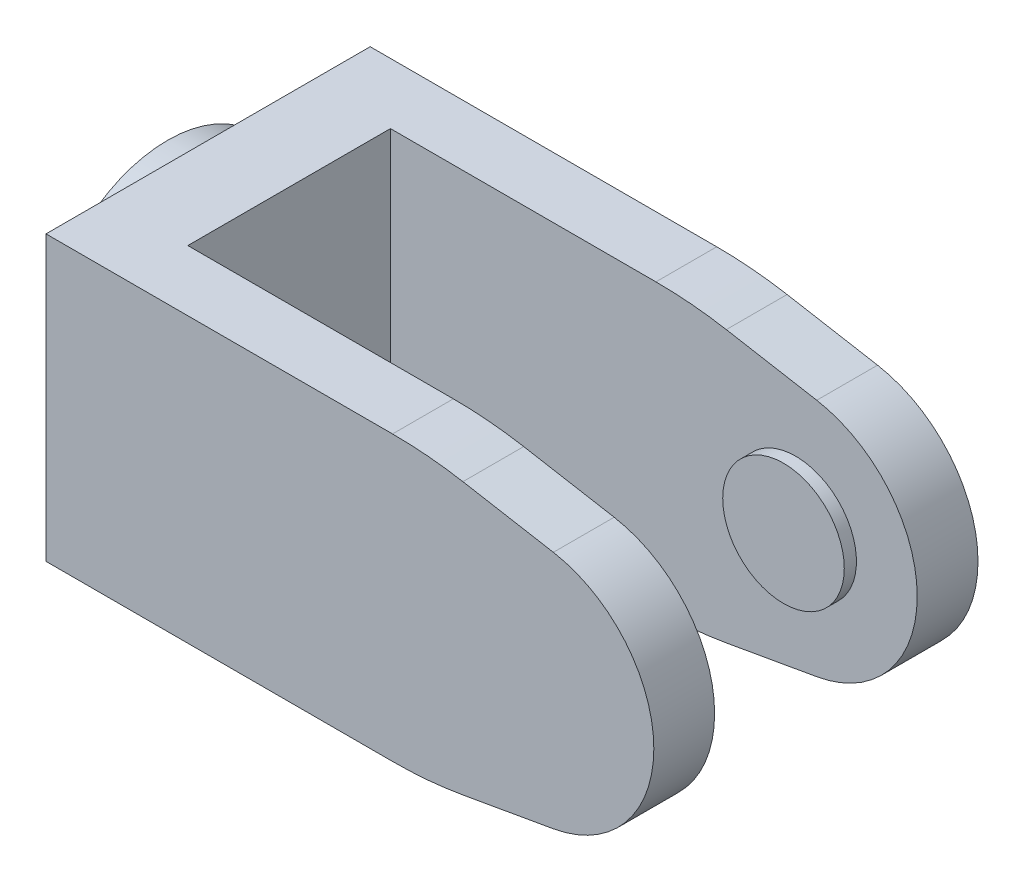
SolidWorks part; units mm, degrees
ref_plane "Front Plane" through (0, 0, 0) normal (0, 0, 1) x (1, 0, 0)
ref_plane "Top Plane" through (0, 0, 0) normal (0, 1, 0) x (1, 0, 0)
ref_plane "Right Plane" through (0, 0, 0) normal (1, 0, 0) x (0, 0, -1)
sketch "Sketch1" plane through (0, 0, 0) normal (0, 0, 1) x (1, 0, 0)
  line L0 (-54.1597, -43.8848) -> (40.1086, -43.8848)
  line L1 (40.1086, -43.8848) -> (71.0498, -38.4291)
  line L2 (71.0498, 20.6594) -> (40.1086, 26.1152)
  line L3 (40.1086, 26.1152) -> (-54.1597, 26.1152)
  line L4 (-54.1597, 26.1152) -> (-54.1597, -43.8848)
  arc A0 (71.0498, -38.4291) -> (71.0498, 20.6594) centre (65.8403, -8.8848) ccw
  dimension "D1" = 170
  dimension "D2" = 170
  dimension "D3" = 70
  dimension "D4" = 120
extrude "Boss-Extrude1" add sketch "Sketch1" along normal mid plane 80
sketch "Sketch2" plane through (0, 0, 0) normal (0, 1, 0) x (1, 0, 0)
  line L0 (40.1086, 40) -> (-54.1597, 40) construction
  line L1 (-34.1597, 25) -> (120.6231, 25)
  line L2 (-34.1597, 25) -> (-34.1597, -25)
  line L3 (-34.1597, -25) -> (120.6231, -25)
  line L4 (120.6231, 25) -> (120.6231, -25)
  line L5 (40.1086, -40) -> (-54.1597, -40) construction
  line L6 (-54.1597, -40) -> (-54.1597, 40) construction
  point P6 (0, 0)
  dimension "D1" = 154.7827
  dimension "D2" = 15
  dimension "D3" = 15
  dimension "D4" = 20
extrude "Cut-Extrude1" cut sketch "Sketch2" against normal through all
extrude "Cut-Extrude2" cut sketch "Sketch2<2>" along normal through all
sketch "Sketch2<2>" plane through (0, 0, 0) normal (0, 1, 0) x (1, 0, 0) same geometry as "Sketch2"
sketch "Sketch3" plane through (0, 0, -25) normal (0, 0, 1) x (1, 0, 0)
  circle A0 centre (65.8403, -8.8848) radius 15
  dimension "D1" = 30
extrude "Boss-Extrude2" add sketch "Sketch3" along normal blind 3
mirror "Mirror1" about plane through (0, 0, 0) normal (0, 0, 1) of "Boss-Extrude2"
sketch "Sketch4" plane through (-54.1597, 0, 0) normal (-1, 0, 0) x (0, 0, 1)
  circle A1 centre (0, -8.8848) radius 30
extrude "Boss-Extrude3" add sketch "Sketch4" along normal blind 10
sketch "Sketch5" plane through (-64.1597, 0, 0) normal (-1, 0, 0) x (0, 0, 1)
  circle A0 centre (0, -8.8848) radius 25
  dimension "D1" = 50
extrude "Boss-Extrude4" add sketch "Sketch5" along normal blind 3
fillet "Fillet1" radius 100 2 edges at (40.1086, 26.1152, 32.5) (40.1086, 26.1152, -32.5)
fillet "Fillet2" radius 100 2 edges at (40.1086, -43.8848, -32.5) (40.1086, -43.8848, 32.5)
